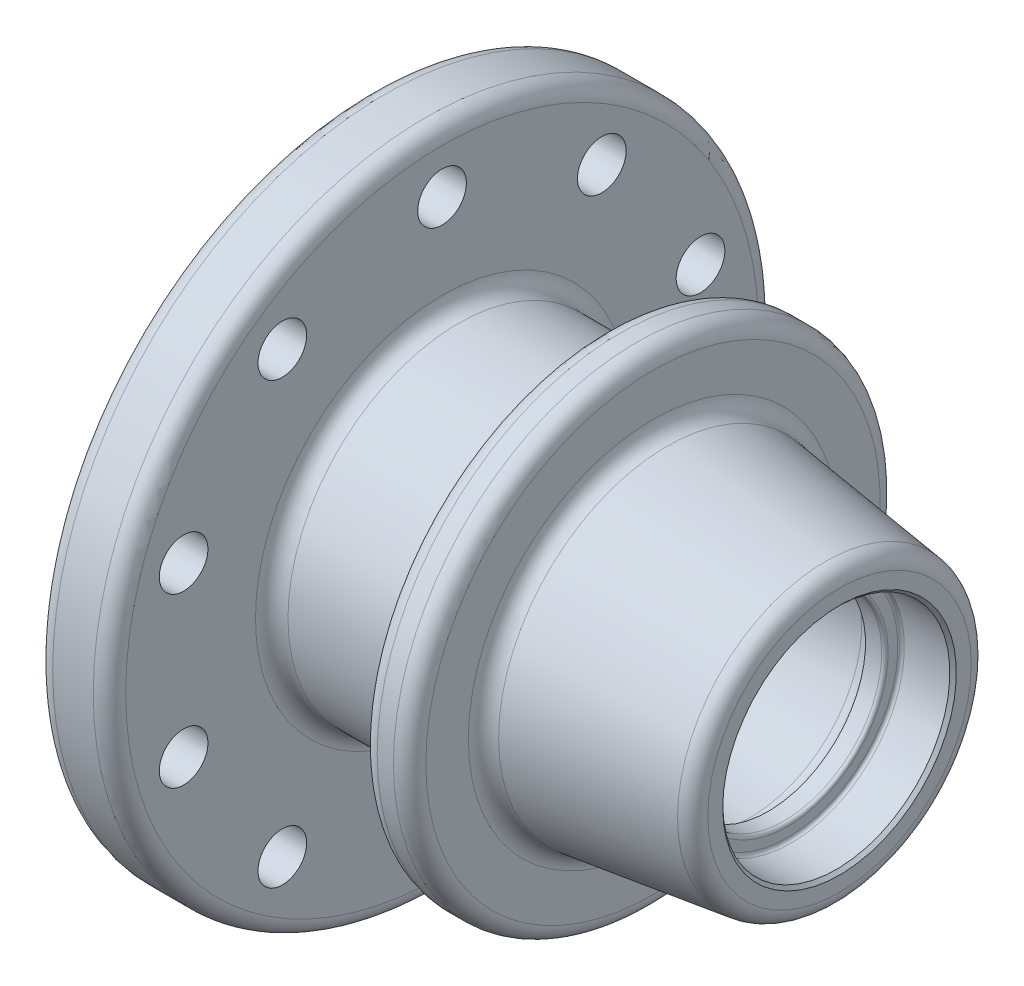
SolidWorks part; units mm, degrees
material "AISI 1020 Steel, Cold Rolled"
ref_plane "Front Plane" through (0, 0, 0) normal (0, 0, 1) x (1, 0, 0)
ref_plane "Top Plane" through (0, 0, 0) normal (0, 1, 0) x (1, 0, 0)
ref_plane "Right Plane" through (0, 0, 0) normal (1, 0, 0) x (0, 0, -1)
sketch "Sketch1" plane through (0, 0, 0) normal (0, 0, 1) x (1, 0, 0)
  line L0 (0, 205) -> (0, 140)
  line L1 (0, 140) -> (-20, 140)
  line L2 (-20, 140) -> (-20, 80)
  line L3 (-20, 80) -> (20, 80)
  line L4 (20, 80) -> (20, 50)
  line L5 (258, 70) -> (290, 70)
  line L6 (65, 44) -> (65, 50)
  line L7 (65, 50) -> (246, 70)
  line L8 (246, 70) -> (246, 60)
  line L9 (246, 60) -> (258, 60)
  line L10 (290, 70) -> (290, 90)
  line L11 (290, 90) -> (175, 105)
  line L12 (175, 105) -> (175, 150)
  line L13 (175, 150) -> (145, 150)
  line L14 (145, 150) -> (145, 105)
  line L15 (145, 105) -> (45, 105)
  line L16 (45, 105) -> (45, 205)
  line L17 (45, 205) -> (0, 205)
  line L18 (-42.4633, 0) -> (142.8069, 0) construction
  line L19 (20, 50) -> (50, 50)
  line L20 (50, 50) -> (50, 44)
  line L21 (50, 44) -> (65, 44)
  line L22 (258, 70) -> (258, 60)
  dimension "D1" = 205
  dimension "D2" = 310
  dimension "D3" = 45
  dimension "D4" = 30
  dimension "D5" = 20
  dimension "D6" = 15
  dimension "D7" = 140
  dimension "D8" = 60
  dimension "D9" = 40
  dimension "D10" = 70
  dimension "D11" = 181
  dimension "D12" = 60
  dimension "D13" = 25
  dimension "D14" = 100
  dimension "D15" = 300
  dimension "D16" = 90
  dimension "D17" = 32
  dimension "D18" = 10
  dimension "D19" = 50
  dimension "D20" = 30
  dimension "D21" = 6
revolve "Revolve1" add sketch "Sketch1" angle 360 about L18
chamfer "Chamfer1" distance 2 angle 45 1 edges at (290, 0, 70)
fillet "Fillet1" radius 10 13 edges at (20, 0, 80) (-20, 0, 80) (-20, 0, 140) (0, 0, 205) (45, 0, 205) (45, 0, 105) (145, 0, 105) (145, 0, 150) (175, 0, 150) (175, 0, 105) (290, 0, 90) (246, 0, 70) (65, 0, 50)
sketch "Sketch2" plane through (0, 0, 0) normal (-1, 0, 0) x (0, 0, 1)
  circle A0 centre (0, 167.5) radius 15
  dimension "D1" = 30
  dimension "D2" = 167.5
extrude "Cut-Extrude1" cut sketch "Sketch2" against normal up to next
pattern_circular "CirPattern1" count 10 over 360 of "Cut-Extrude1"
fillet "Fillet2" radius 1.5 4 edges at (65, 0, 44) (20, 0, 50) (50, 0, 44) (50, 0, 50)
fillet "Fillet3" radius 2 2 edges at (258, 0, 60) (258, 0, 70)
sketch "Sketch3" plane through (-20, 0, 0) normal (-1, 0, 0) x (0, 0, 1)
  circle A0 centre (0, 109) radius 5
  dimension "D1" = 10
  dimension "D2" = 109
extrude "Cut-Extrude2" cut sketch "Sketch3" against normal blind 15
pattern_circular "CirPattern2" count 6 over 360 about axis through (-42.4633, 0, 0) along (-1, 0, 0) of "Cut-Extrude2"
